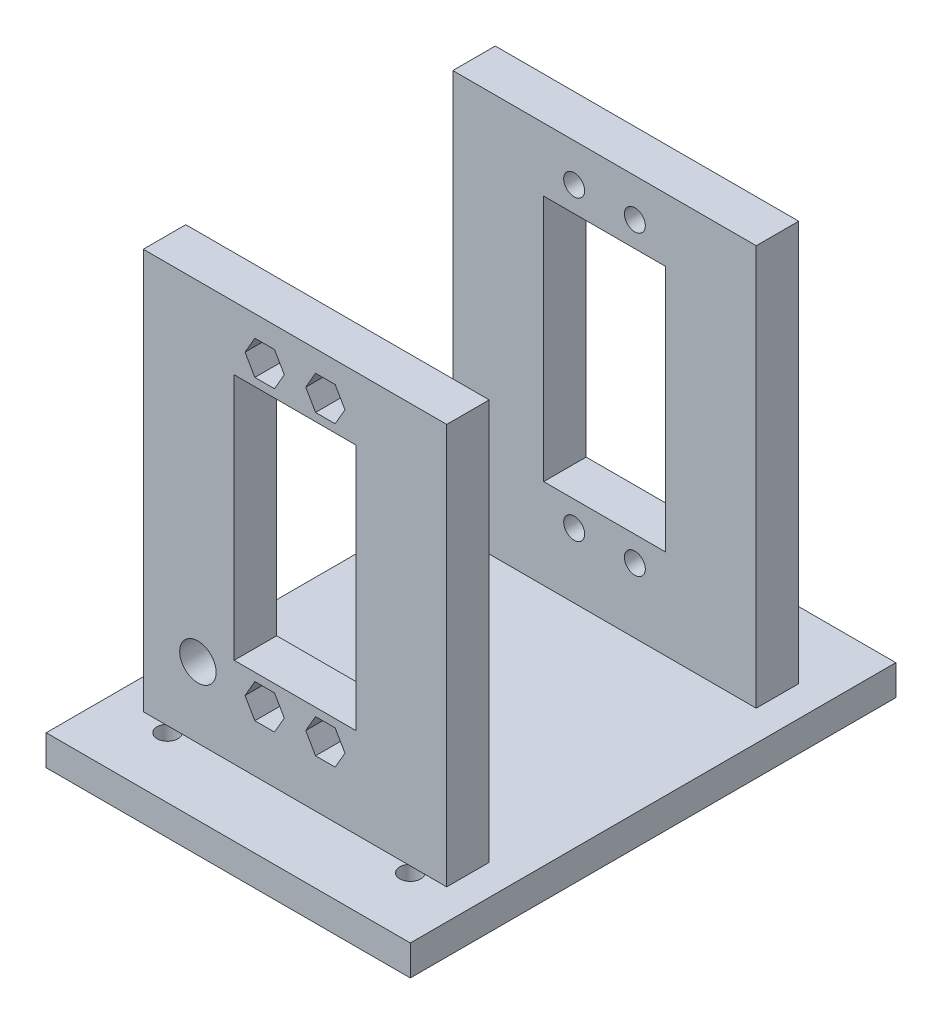
SolidWorks part; units mm, degrees
material "PLA Makeshift"
ref_plane "Front Plane" through (0, 0, 0) normal (0, 0, 1) x (1, 0, 0)
ref_plane "Top Plane" through (0, 0, 0) normal (0, 1, 0) x (1, 0, 0)
ref_plane "Right Plane" through (0, 0, 0) normal (1, 0, 0) x (0, 0, -1)
sketch "Sketch1" plane through (0, 0, 0) normal (0, 1, 0) x (1, 0, 0)
  line L1 (-30, -40) -> (30, -40)
  line L2 (-30, -40) -> (-30, 40)
  line L3 (-30, 40) -> (30, 40)
  line L4 (30, -40) -> (30, 40)
  line L5 (-30, -40) -> (30, 40) construction
  line L6 (-30, 40) -> (30, -40) construction
  point P0 (0, 0)
  dimension "D1" = 80
  dimension "D2" = 60
extrude "Boss-Extrude1" add sketch "Sketch1" along normal mid plane 5
sketch "Sketch2" plane through (0, 2.5, 0) normal (0, 1, 0) x (1, 0, 0)
  line L0 (30, -40) -> (30, 40) construction
  line L2 (-30, 40) -> (-30, -40) construction
  line L3 (-30, -40) -> (30, -40) construction
  circle A0 centre (-20, 30) radius 1.725
  circle A1 centre (20, 30) radius 1.725
  circle A2 centre (20, -30) radius 1.725
  circle A3 centre (-20, -30) radius 1.725
  dimension "D1" = 3.45
  dimension "D2" = 40
  dimension "D3" = 10
  dimension "D4" = 60
  dimension "D5" = 60
  dimension "D6" = 40
  dimension "D7" = 10
  dimension "D8" = 10
  dimension "D9" = 10
extrude "Cut-Extrude1" cut sketch "Sketch2" against normal through all
ref_plane "Plane1" through (0, 0, 22) normal (0, 0, 1) x (1, 0, 0)
sketch "Sketch3" plane through (0, 0, 22) normal (0, 0, 1) x (1, 0, 0)
  line L1 (-25, 2.5) -> (25, 2.5)
  line L2 (-25, 2.5) -> (-25, 68.5)
  line L3 (-25, 68.5) -> (25, 68.5)
  line L4 (25, 2.5) -> (25, 68.5)
  dimension "D1" = 50
  dimension "D2" = 25
  dimension "D3" = 66
  dimension "D4" = 2.5
extrude "Boss-Extrude2" add sketch "Sketch3" along normal blind 7
mirror "Mirror1" about plane through (0, 0, 0) normal (0, 0, 1) of "Boss-Extrude2"
sketch "Sketch4" plane through (0, 0, 29) normal (0, 0, 1) x (1, 0, 0)
  line L1 (-10.025, 58.075) -> (10.025, 58.075)
  line L2 (-10.025, 58.075) -> (-10.025, 17.325)
  line L3 (-10.025, 17.325) -> (10.025, 17.325)
  line L4 (10.025, 58.075) -> (10.025, 17.325)
  dimension "D1" = 20.05
  dimension "D2" = 10.025
  dimension "D3" = 40.75
  dimension "D4" = 17.325
extrude "Cut-Extrude2" cut sketch "Sketch4" against normal through all
sketch "Sketch5" plane through (0, 0, 29) normal (0, 0, 1) x (1, 0, 0)
  circle A0 centre (-5, 62.2) radius 1.725
  circle A1 centre (5, 62.2) radius 1.725
  circle A2 centre (-5, 13.2) radius 1.725
  circle A3 centre (5, 13.2) radius 1.725
  dimension "D9" = 3.45
  dimension "D1" = 5
  dimension "D2" = 5
  dimension "D3" = 13.2
  dimension "D4" = 13.2
  dimension "D5" = 62.2
  dimension "D6" = 62.2
  dimension "D7" = 5
  dimension "D8" = 5
extrude "Cut-Extrude3" cut sketch "Sketch5" against normal through all
sketch "Sketch6" plane through (0, 0, 29) normal (0, 0, 1) x (1, 0, 0)
  line L1 (-1.7668, 62.2) -> (-3.3834, 65)
  line L2 (-3.3834, 65) -> (-6.6166, 65)
  line L3 (-6.6166, 65) -> (-8.2332, 62.2)
  line L4 (-8.2332, 62.2) -> (-6.6166, 59.4)
  line L5 (-6.6166, 59.4) -> (-3.3834, 59.4)
  line L6 (-3.3834, 59.4) -> (-1.7668, 62.2)
  line L7 (1.7668, 62.2) -> (3.3834, 59.4)
  line L8 (3.3834, 59.4) -> (6.6166, 59.4)
  line L9 (6.6166, 59.4) -> (8.2332, 62.2)
  line L10 (8.2332, 62.2) -> (6.6166, 65)
  line L11 (6.6166, 65) -> (3.3834, 65)
  line L12 (3.3834, 65) -> (1.7668, 62.2)
  line L13 (-1.7668, 13.2) -> (-3.3834, 16)
  line L14 (-3.3834, 16) -> (-6.6166, 16)
  line L15 (-6.6166, 16) -> (-8.2332, 13.2)
  line L16 (-8.2332, 13.2) -> (-6.6166, 10.4)
  line L17 (-6.6166, 10.4) -> (-3.3834, 10.4)
  line L18 (-3.3834, 10.4) -> (-1.7668, 13.2)
  line L19 (8.2332, 13.2) -> (6.6166, 16)
  line L20 (6.6166, 16) -> (3.3834, 16)
  line L21 (3.3834, 16) -> (1.7668, 13.2)
  line L22 (1.7668, 13.2) -> (3.3834, 10.4)
  line L23 (3.3834, 10.4) -> (6.6166, 10.4)
  line L24 (6.6166, 10.4) -> (8.2332, 13.2)
  circle A0 centre (-5, 62.2) radius 2.8 construction
  circle A1 centre (5, 62.2) radius 2.8 construction
  circle A2 centre (-5, 13.2) radius 2.8 construction
  circle A3 centre (5, 13.2) radius 2.8 construction
extrude "Cut-Extrude4" cut sketch "Sketch6" against normal blind 4.2
mirror "Mirror3" about plane through (0, 0, 0) normal (0, 0, 1) of "Cut-Extrude4"
sketch "Sketch7" plane through (0, 0, 0) normal (0, 0, 1) x (1, 0, 0)
  circle A0 centre (-16, 14.1) radius 3
extrude "Cut-Extrude5" cut sketch "Sketch7" along normal blind 9 from offset 21
